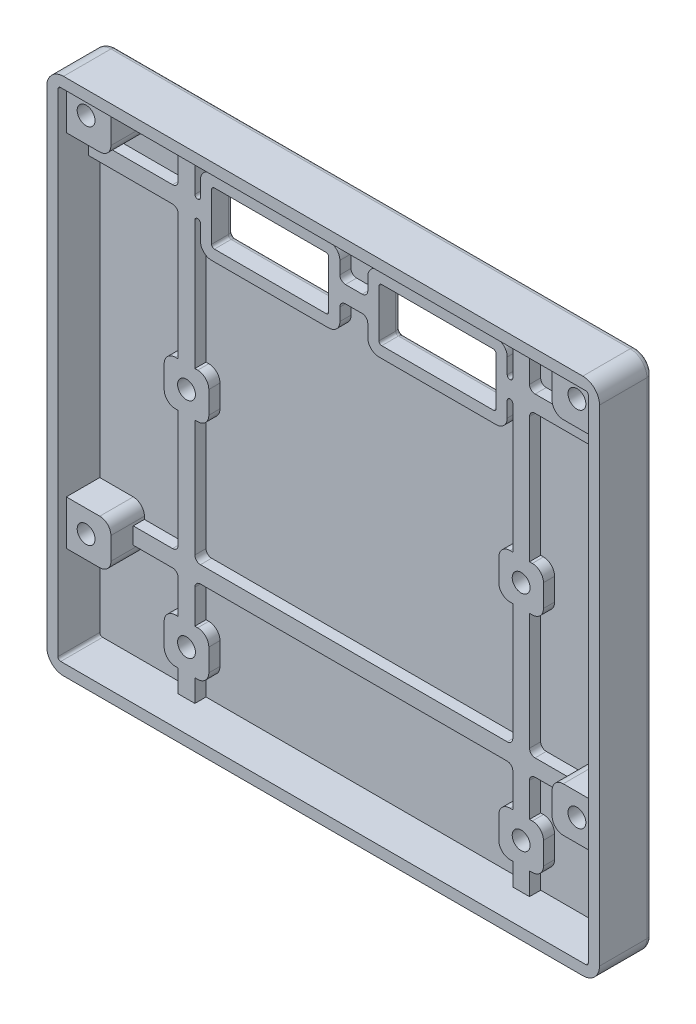
SolidWorks part; units mm, degrees
ref_plane "Спереди" through (0, 0, 0) normal (0, 0, 1) x (1, 0, 0)
ref_plane "Сверху" through (0, 0, 0) normal (0, 1, 0) x (1, 0, 0)
ref_plane "Справа" through (0, 0, 0) normal (1, 0, 0) x (0, 0, -1)
sketch "Эскиз1" plane through (0, 0, 0) normal (0, 0, 1) x (1, 0, 0)
  line L1 (-49.55, -46.55) -> (49.55, -46.55)
  line L2 (-49.55, -46.55) -> (-49.55, 46.55)
  line L3 (-49.55, 46.55) -> (49.55, 46.55)
  line L4 (49.55, -46.55) -> (49.55, 46.55)
  line L5 (-49.55, -46.55) -> (49.55, 46.55) construction
  line L6 (-49.55, 46.55) -> (49.55, -46.55) construction
  point P0 (0, 0)
  dimension "D1" = 93.1
  dimension "D2" = 99.1
extrude "Бобышка-Вытянуть1" add sketch "Эскиз1" along normal blind 2
sketch "Эскиз2" plane through (0, 0, 2) normal (0, 0, 1) x (1, 0, 0)
  line L0 (-43.55, -24) -> (43.55, -24) construction
  line L1 (47.55, -44.55) -> (-47.55, -44.55)
  line L2 (47.55, -44.55) -> (47.55, 44.55)
  line L3 (47.55, 44.55) -> (-47.55, 44.55)
  line L4 (-47.55, -44.55) -> (-47.55, 44.55)
  line L5 (47.55, -44.55) -> (-47.55, 44.55) construction
  line L6 (47.55, 44.55) -> (-47.55, -44.55) construction
  line L7 (49.55, -46.55) -> (-49.55, -46.55)
  line L8 (49.55, -46.55) -> (49.55, 46.55)
  line L9 (49.55, 46.55) -> (-49.55, 46.55)
  line L10 (-49.55, -46.55) -> (-49.55, 46.55)
  line L11 (49.55, -46.55) -> (-49.55, 46.55) construction
  line L12 (49.55, 46.55) -> (-49.55, -46.55) construction
  line L13 (-47.55, 44.55) -> (-39.55, 44.55)
  line L14 (-47.55, 44.55) -> (-47.55, 36.55)
  line L15 (-47.55, 36.55) -> (-39.55, 36.55)
  line L16 (-39.55, 44.55) -> (-39.55, 36.55)
  line L17 (-47.55, 44.55) -> (-39.55, 36.55) construction
  line L18 (-47.55, 36.55) -> (-39.55, 44.55) construction
  line L19 (39.55, 44.55) -> (47.55, 44.55)
  line L20 (39.55, 44.55) -> (39.55, 36.55)
  line L21 (39.55, 36.55) -> (47.55, 36.55)
  line L22 (47.55, 44.55) -> (47.55, 36.55)
  line L23 (39.55, 44.55) -> (47.55, 36.55) construction
  line L24 (39.55, 36.55) -> (47.55, 44.55) construction
  line L25 (39.55, -20) -> (47.55, -20)
  line L26 (39.55, -20) -> (39.55, -28)
  line L27 (39.55, -28) -> (47.55, -28)
  line L28 (47.55, -20) -> (47.55, -28)
  line L29 (39.55, -20) -> (47.55, -28) construction
  line L30 (39.55, -28) -> (47.55, -20) construction
  line L31 (-47.55, -20) -> (-39.55, -20)
  line L32 (-47.55, -20) -> (-47.55, -28)
  line L33 (-47.55, -28) -> (-39.55, -28)
  line L34 (-39.55, -20) -> (-39.55, -28)
  line L35 (-47.55, -20) -> (-39.55, -28) construction
  line L36 (-47.55, -28) -> (-39.55, -20) construction
  line L37 (0, 75.6785) -> (0, 254.2532) construction
  line L38 (-39.55, -22.5) -> (-31.5, -22.5)
  line L39 (39.55, -25.5) -> (31.5, -25.5)
  line L40 (-31.5, -32.55) -> (-31.5, -25.5)
  line L41 (-28.5, -32.55) -> (-28.5, -25.5)
  line L42 (-31.5, -40.55) -> (-31.5, -44.55)
  line L43 (-28.5, -40.55) -> (-28.5, -44.55)
  line L44 (-30, 50.642) -> (-30, -75.1873) construction
  line L45 (30, 50.642) -> (30, -75.1873) construction
  line L46 (-15, 32.5) -> (15, 32.5) construction
  line L47 (-31.5, -22.5) -> (-31.5, -0.55)
  line L48 (-25.5, 27.75) -> (-4.5, 27.75)
  line L49 (-25.5, 27.75) -> (-25.5, 37.25)
  line L50 (-25.5, 37.25) -> (-4.5, 37.25)
  line L51 (-4.5, 27.75) -> (-4.5, 37.25)
  line L52 (-25.5, 27.75) -> (-4.5, 37.25) construction
  line L53 (-25.5, 37.25) -> (-4.5, 27.75) construction
  line L54 (25.5, 27.75) -> (4.5, 27.75)
  line L55 (25.5, 27.75) -> (25.5, 37.25)
  line L56 (25.5, 37.25) -> (4.5, 37.25)
  line L57 (4.5, 27.75) -> (4.5, 37.25)
  line L58 (25.5, 27.75) -> (4.5, 37.25) construction
  line L59 (25.5, 37.25) -> (4.5, 27.75) construction
  line L60 (-27.5, 25.75) -> (-2.5, 25.75)
  line L61 (-27.5, 25.75) -> (-27.5, 39.25)
  line L62 (-27.5, 39.25) -> (-2.5, 39.25)
  line L63 (-2.5, 25.75) -> (-2.5, 39.25)
  line L64 (-27.5, 25.75) -> (-2.5, 39.25) construction
  line L65 (-27.5, 39.25) -> (-2.5, 25.75) construction
  line L66 (2.5, 25.75) -> (27.5, 25.75)
  line L67 (2.5, 25.75) -> (2.5, 39.25)
  line L68 (2.5, 39.25) -> (27.5, 39.25)
  line L69 (27.5, 25.75) -> (27.5, 39.25)
  line L70 (2.5, 25.75) -> (27.5, 39.25) construction
  line L71 (2.5, 39.25) -> (27.5, 25.75) construction
  line L72 (-34, -0.55) -> (-26, -0.55)
  line L73 (-34, -0.55) -> (-34, 7.45)
  line L74 (-34, 7.45) -> (-26, 7.45)
  line L75 (-26, -0.55) -> (-26, 7.45)
  line L76 (-34, -0.55) -> (-26, 7.45) construction
  line L77 (-34, 7.45) -> (-26, -0.55) construction
  line L78 (26, -0.55) -> (34, -0.55)
  line L79 (26, -0.55) -> (26, 7.45)
  line L80 (26, 7.45) -> (34, 7.45)
  line L81 (34, -0.55) -> (34, 7.45)
  line L82 (26, -0.55) -> (34, 7.45) construction
  line L83 (26, 7.45) -> (34, -0.55) construction
  line L84 (34, -40.55) -> (26, -40.55)
  line L85 (34, -40.55) -> (34, -32.55)
  line L86 (34, -32.55) -> (26, -32.55)
  line L87 (26, -40.55) -> (26, -32.55)
  line L88 (34, -40.55) -> (26, -32.55) construction
  line L89 (34, -32.55) -> (26, -40.55) construction
  line L90 (-34, -32.55) -> (-26, -32.55)
  line L91 (-34, -32.55) -> (-34, -40.55)
  line L92 (-34, -40.55) -> (-26, -40.55)
  line L93 (-26, -32.55) -> (-26, -40.55)
  line L94 (-34, -32.55) -> (-26, -40.55) construction
  line L95 (-34, -40.55) -> (-26, -32.55) construction
  line L96 (-28.5, -22.5) -> (-28.5, -0.55)
  line L97 (-28.5, 7.45) -> (-28.5, 31)
  line L98 (-31.5, 7.45) -> (-31.5, 31)
  line L99 (28.5, -25.5) -> (28.5, -32.55)
  line L100 (31.5, -32.55) -> (31.5, -25.5)
  line L101 (31.5, -40.55) -> (31.5, -44.55)
  line L102 (28.5, -40.55) -> (28.5, -44.55)
  line L103 (28.5, -22.5) -> (28.5, -0.55)
  line L104 (28.5, 7.45) -> (28.5, 31)
  line L105 (31.5, -22.5) -> (31.5, -0.55)
  line L106 (31.5, 7.45) -> (31.5, 31)
  line L107 (-27.5, 34) -> (-28.5, 34)
  line L108 (-31.5, 34) -> (-47.55, 34)
  line L109 (-47.55, 31) -> (-31.5, 31)
  line L110 (-28.5, 31) -> (-27.5, 31)
  line L111 (-2.5, 31) -> (2.5, 31)
  line L112 (27.5, 31) -> (28.5, 31)
  line L113 (31.5, 31) -> (47.55, 31)
  line L114 (47.55, 34) -> (31.5, 34)
  line L115 (28.5, 34) -> (27.5, 34)
  line L116 (-2.5, 34) -> (2.5, 34)
  line L117 (-31.5, 34) -> (-31.5, 44.55)
  line L118 (-28.5, 34) -> (-28.5, 44.55)
  line L119 (28.5, 34) -> (28.5, 44.55)
  line L120 (31.5, 34) -> (31.5, 44.55)
  line L121 (31.5, -22.5) -> (39.55, -22.5)
  line L122 (28.5, -25.5) -> (-28.5, -25.5)
  line L123 (-31.5, -25.5) -> (-39.55, -25.5)
  line L124 (-28.5, -22.5) -> (28.5, -22.5)
  circle A0 centre (-44, 41) radius 1.6
  circle A1 centre (44, 41) radius 1.6
  circle A2 centre (-44, -24) radius 1.6
  circle A3 centre (44, -24) radius 1.6
  circle A4 centre (-30, -36.55) radius 1.6
  circle A5 centre (-30, 3.45) radius 1.6
  circle A6 centre (30, 3.45) radius 1.6
  circle A7 centre (30, -36.55) radius 1.6
  point P0 (0, 0)
  point P6 (0, 0)
  point P12 (-43.55, 40.55)
  point P17 (43.55, 40.55)
  point P22 (43.55, -24)
  point P27 (-43.55, -24)
  point P42 (2, -24)
  point P63 (0, 32.5)
  line M18 (49.55, -46.55) -> (49.55, 46.55)
  line M19 (49.55, 46.55) -> (-49.55, 46.55)
  line M20 (-49.55, 46.55) -> (-49.55, -46.55)
  line M21 (-49.55, -46.55) -> (49.55, -46.55)
  dimension "D4" = 3.2
  dimension "D1" = 89.1
  dimension "D2" = 95.1
  dimension "D3" = 88
  dimension "D5" = 8
  dimension "D6" = 65
  dimension "D10" = 40
  dimension "D11" = 10
  dimension "D12" = 32.5
  dimension "D13" = 30
  dimension "D8" = 30
  dimension "D9" = 30
  dimension "D14" = 9.5
  dimension "D15" = 21
  dimension "D16" = 2
  dimension "D17" = 2
  dimension "D7" = 1.5
  dimension "D18" = 1.5
  dimension "D19" = 1.5
  dimension "D20" = 1.5
  dimension "D21" = 1.5
  dimension "D22" = 1.5
  dimension "D23" = 1.5
  dimension "D24" = 1.5
extrude "Бобышка-Вытянуть2" add sketch "Эскиз2" along normal blind 7.5 contours L1 L4 L3 L2 M21 M18 M19 M20 region at (0, -45.1903, 2)
extrude "Бобышка-Вытянуть3" add sketch "Эскиз2<3>" along normal blind 6 contours L15 L16 L13 L14 | L33 L34 L31 L32 | L21 L22 L19 L20 | L27 L28 L25 L26
sketch "Эскиз2<3>" plane through (0, 0, 2) normal (0, 0, 1) x (1, 0, 0) same geometry as "Эскиз2"
extrude "Бобышка-Вытянуть4" add sketch "Эскиз2<4>" along normal blind 2 contours L107 L118 L3 L117 L108 L4 L109 L98 L74 L97 L110 L61 | L116 L63 L111 L67 | L60 L63 L62 L61 L51 L48 L49 L50 | L66 L69 L68 L67 L54 L57 L56 L55 | L114 L120 L3 L119 L115 L69 L112 L104 L80 L106 L113 L2 | L78 L81 L80 L79 A6 | L124 L96 L72 L47 L38 L34 L123 L40 L90 L41 L122 L99 L86 L100 L39 L26 L121 L105 L78 L103 | L93 L90 L91 L92 A4 | L92 L42 L1 L43 | L72 L75 L74 L73 A5 | L87 L84 L85 L86 A7 | L84 L102 L1 L101 region at (30, -42.55, 2) region at (30, -40.4369, 2) region at (-30, -42.55, 2) region at (39.525, 31.4217, 2) region at (35.525, -24.6467, 2) region at (-30, -40.4369, 2) region at (32.75, 7.3369, 2) region at (-47.1283, 32.5, 2) region at (27.2159, 28.375, 2) region at (-30, 7.3369, 2) region at (-27.2159, 36.625, 2) region at (0, 32.5, 2)
sketch "Эскиз2<4>" plane through (0, 0, 2) normal (0, 0, 1) x (1, 0, 0) same geometry as "Эскиз2"
extrude "Вырез-Вытянуть1" cut sketch "Эскиз2<5>" along normal through all both and the other way through all contours L48 L51 L50 L49 | L57 L54 L55 L56 | A0 | A5 | A2 | A4 | A7 | A3 | A6 | A1 region at (-15, 32.5, 2) region at (15, 32.5, 2) region at (-44, 41, 2) region at (44, 41, 2) region at (-44, -24, 2) region at (44, -24, 2) region at (-30, -36.55, 2) region at (-30, 3.45, 2) region at (30, 3.45, 2) region at (30, -36.55, 2)
sketch "Эскиз2<5>" plane through (0, 0, 2) normal (0, 0, 1) x (1, 0, 0) same geometry as "Эскиз2"
fillet "Скругление1" radius 3 4 edges at (-49.55, 46.55, 4.75) (49.55, 46.55, 4.75) (49.55, -46.55, 4.75) (-49.55, -46.55, 4.75)
fillet "Скругление2" radius 2 30 edges at (39.55, 36.55, 5) (39.55, -20, 5) (39.55, -28, 5) (-39.55, -28, 5) (-39.55, -20, 5) (-39.55, 36.55, 5) (34, -40.55, 3) (34, -32.55, 3) (26, -32.55, 3) (26, -40.55, 3) (-26, -32.55, 3) (-26, -40.55, 3) (-34, -40.55, 3) (-34, -32.55, 3) (34, 7.45, 3) (34, -0.55, 3) (26, -0.55, 3) (26, 7.45, 3) (-34, 7.45, 3) (-26, 7.45, 3) (-34, -0.55, 3) (-26, -0.55, 3) (27.5, 39.25, 3) (2.5, 39.25, 3) (-2.5, 39.25, 3) (-27.5, 39.25, 3) (27.5, 25.75, 3) (2.5, 25.75, 3) (-2.5, 25.75, 3) (-27.5, 25.75, 3)
fillet "Скругление3" radius 0.5 8 edges at (25.5, 37.25, 2) (25.5, 27.75, 2) (4.5, 37.25, 2) (4.5, 27.75, 2) (-4.5, 27.75, 2) (-4.5, 37.25, 2) (-25.5, 27.75, 2) (-25.5, 37.25, 2)
fillet "Скругление4" radius 0.5 12 edges at (28.5, 34, 3) (27.5, 34, 3) (28.5, 31, 3) (27.5, 31, 3) (-27.5, 34, 3) (-27.5, 31, 3) (-28.5, 34, 3) (-28.5, 31, 3) (47.55, -44.55, 5.75) (47.55, 44.55, 8.75) (-47.55, 44.55, 8.75) (-47.55, -44.55, 5.75)
fillet "Скругление5" radius 1 16 edges at (31.5, 31, 3) (31.5, 34, 3) (31.5, -22.5, 3) (28.5, -22.5, 3) (31.5, -25.5, 3) (28.5, -25.5, 3) (-28.5, -25.5, 3) (-31.5, -25.5, 3) (-28.5, -22.5, 3) (-31.5, -22.5, 3) (-31.5, 34, 3) (-31.5, 31, 3) (-2.5, 31, 3) (2.5, 31, 3) (2.5, 34, 3) (-2.5, 34, 3)
fillet "Скругление6" radius 1 24 edges at (25.3536, 37.1036, 0) (25.5, 32.5, 0) (25.3536, 27.8964, 0) (15, 27.75, 0) (4.6464, 27.8964, 0) (4.5, 32.5, 0) (4.6464, 37.1036, 0) (-25.3536, 37.1036, 0) (-25.5, 32.5, 0) (-25.3536, 27.8964, 0) (-15, 27.75, 0) (-4.6464, 27.8964, 0) (-4.5, 32.5, 0) (-4.6464, 37.1036, 0) (-48.6713, -45.6713, 0) (-49.55, 0, 0) (-48.6713, 45.6713, 0) (0, 46.55, 0) (48.6713, 45.6713, 0) (49.55, 0, 0) (48.6713, -45.6713, 0) (15, 37.25, 0) (-15, 37.25, 0) (0, -46.55, 0)
equation "\"Зазор\"= 0.1"
equation "\"Толщина стенок\"= 2"
equation "\"D2@Эскиз1\"=93+\"Зазор\"+(\"Толщина стенок\"+\"Толщина направляющей стенки\"+\"Зазор\"*2)*2"
equation "\"D1@Эскиз1\"=87+\"Зазор\"+(\"Толщина стенок\"+\"Толщина направляющей стенки\"+\"Зазор\"*2)*2"
equation "\"D1@Бобышка-Вытянуть1\"=\"Толщина стенок\""
equation "\"D1@Эскиз2\"=87+\"Зазор\"+(\"Толщина направляющей стенки\"+\"Зазор\"*2)*2"
equation "\"D2@Эскиз2\"=93+\"Зазор\"+(\"Толщина направляющей стенки\"+\"Зазор\"*2)*2"
equation "\"D1@Бобышка-Вытянуть2\"=1.5+9-\"Толщина стенок\"-1"
equation "\"D1@Бобышка-Вытянуть3\"=9-\"Толщина стенок\"-1"
equation "\"D12@Эскиз2\"=87/2-11"
equation "\"Толщина направляющей стенки\"= 0.8"
